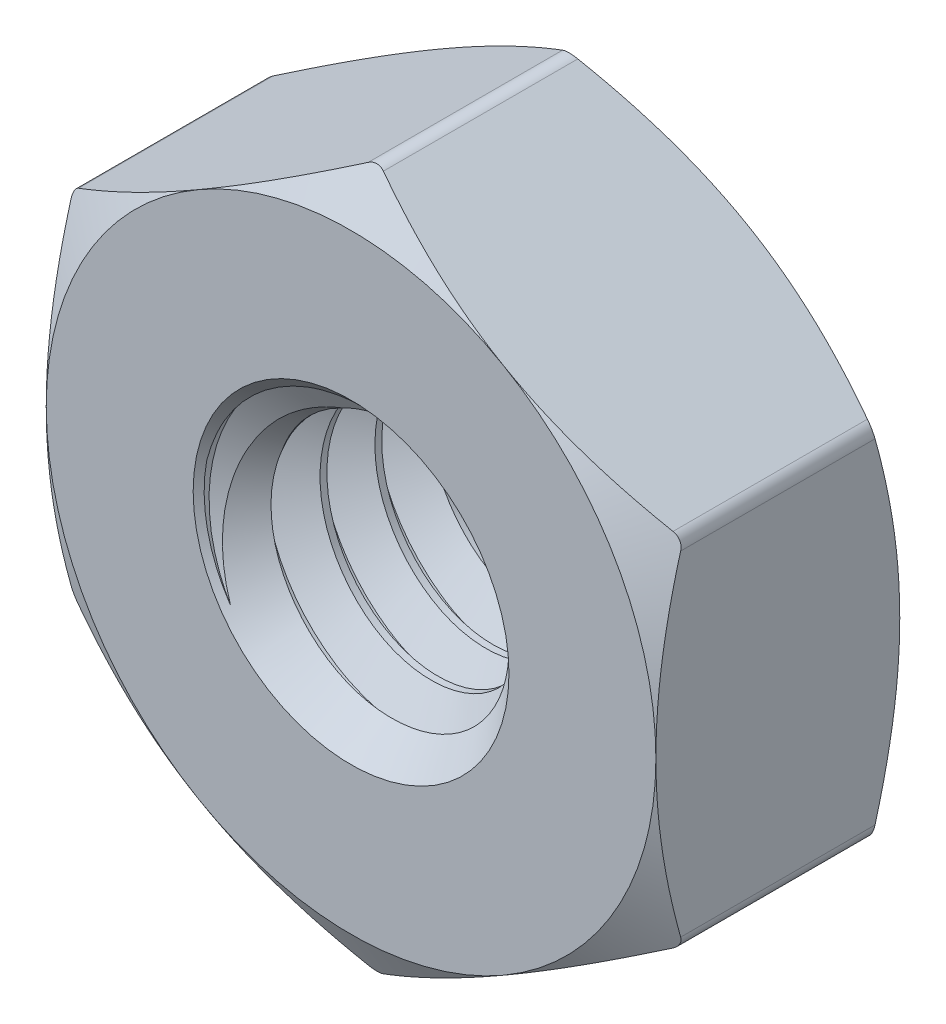
SolidWorks part; units mm, degrees
ref_plane "Front" through (0, 0, 0) normal (0, 0, 1) x (1, 0, 0)
ref_plane "Top" through (0, 0, 0) normal (0, 1, 0) x (1, 0, 0)
ref_plane "Right" through (0, 0, 0) normal (1, 0, 0) x (0, 0, -1)
sketch "Sketch1" plane through (0, 0, 0) normal (0, 0, 1) x (1, 0, 0)
  line L0 (0, 1.25) -> (0, 0.8) construction
  line L1 (-2.5, 1.4434) -> (-2.5, -1.4434)
  line L2 (-2.5, -1.4434) -> (0, -2.8868)
  line L3 (0, -2.8868) -> (2.5, -1.4434)
  line L4 (2.5, -1.4434) -> (2.5, 1.4434)
  line L5 (2.5, 1.4434) -> (0, 2.8868)
  line L6 (0, 2.8868) -> (-2.5, 1.4434)
  circle A0 centre (0, 0) radius 2.5 construction
  circle A1 centre (0, 0) radius 1.25 construction
  point P10 (0, 1.25)
  dimension "Width" = 5
  dimension "Thread Size" = 2.5
  dimension "Thread Pitch" = 0.45
sketch "Sketch2" plane through (0, 0, 0) normal (1, 0, 0) x (0, 0, -1)
  line L0 (-1, 0) -> (1, 0) construction
  line L1 (-1, 2.8868) -> (1, 2.8868) construction
  dimension "Height" = 2
sketch "Sketch15" plane through (0, 0, 0) normal (0, 0, 1) x (1, 0, 0)
  line L1 (0, 2.8868) -> (-2.5, 1.4434)
  line L2 (-2.5, 1.4434) -> (-2.5, -1.4434)
  line L3 (-2.5, -1.4434) -> (0, -2.8868)
  line L4 (0, -2.8868) -> (2.5, -1.4434)
  line L5 (2.5, -1.4434) -> (2.5, 1.4434)
  line L6 (2.5, 1.4434) -> (0, 2.8868)
  circle A0 centre (0, 0) radius 2.5 construction
extrude "Boss-Extrude2" add sketch "Sketch15" along normal mid plane 2
sketch "Sketch16" plane through (0, 0, 0) normal (0, 0, 1) x (1, 0, 0)
  circle A0 centre (0, 0) radius 1.25 construction
  circle A1 centre (0, 0) radius 1.25
sketch "Sketch4" plane through (0, 0, -1) normal (0, 0, -1) x (-1, 0, 0)
  circle A0 centre (0, 0) radius 1.25 construction
  circle A1 centre (0, 0) radius 1.25
extrude "Cut-Extrude4" cut sketch "Sketch16" against normal through all both and the other way through all
sketch "Sketch7" plane through (0, 0, 1) normal (0, 0, 1) x (1, 0, 0)
  circle A0 centre (0, 0) radius 2.5 construction
  circle A1 centre (0, 0) radius 2.5
extrude "Cut-Extrude5" cut sketch "Sketch7" against normal through all draft 60 flip side to cut
mirror "Mirror4" about plane through (0, 0, 0) normal (0, 0, 1) of "Cut-Extrude5"
fillet "Fillet2" radius 0.125 6 edges at (-2.5, 1.4434, 0) (-2.5, -1.4434, 0) (0, -2.8868, 0) (2.5, -1.4434, 0) (2.5, 1.4434, 0) (0, 2.8868, 0)
sketch "Sketch8" plane through (0, 0, 1) normal (0, 0, 1) x (1, 0, 0)
  line L0 (0.3235, -1.2074) -> (0, 0) construction
  line L2 (0, 1.25) -> (0, 0.8) construction
  circle A0 centre (0, 0) radius 1.25 construction
  point P0 (0.3235, -1.2074)
  dimension "D1" = 15
sketch "Sketch13" plane through (0, 0, -1) normal (0, 0, -1) x (-1, 0, 0)
  circle A0 centre (0, 0) radius 1.25 construction
  circle A1 centre (0, 0) radius 1.25
extrude "Boss-Extrude1" add sketch "Sketch13" against normal up to surface (2 mm away) separate body up to face at (1.25, 0, 1)
curve "Helix/Spiral3" pitch 0.45 height 2.9 radius 1.25 centre (0, 0, -1) axis (0, 0, 1) start towards (0, 1, 0)
sketch "Sketch12" plane through (0, 0, 0) normal (1, 0, 0) x (0, 0, -1)
  line L0 (1.3938, 1.25) -> (1, 1.25)
  line L1 (1.3938, 1.25) -> (1.225, 0.9577)
  line L2 (1.225, 0.9577) -> (1.1688, 0.9577)
  line L3 (1.1688, 0.9577) -> (1, 1.25)
  line L4 (1.1969, 0.9577) -> (1.1969, 1.25) construction
  line L5 (1.0844, 1.1039) -> (1.3094, 1.1039) construction
  dimension "D1" = 60
  dimension "D2" = 0.0563
  dimension "D3" = 0.225
sweep "Cut-Sweep1" cut profiles "Sketch12" path "Helix/Spiral3" align with end faces yes
sketch "Sketch17" plane through (0, 0, 1) normal (0, 0, 1) x (1, 0, 0)
  circle A1 centre (0, 0) radius 1.25
  circle A2 centre (0, 0) radius 1.25
  dimension "D1" = 0
extrude "Boss-Extrude3" add sketch "Sketch17" against normal up to surface (2 mm away) up to face at (1.25, 0, -1)
combine bodies "Combine1" operation type subtract main body 127 bodies to subtract 118
sketch "Sketch10" plane through (0, 0, 1) normal (0, 0, 1) x (1, 0, 0)
  circle A0 centre (0, 0) radius 1.25 construction
  circle A1 centre (0, 0) radius 1.25 construction
  circle A2 centre (0, 0) radius 1.295
  dimension "D1" = 0.045
extrude "Cut-Extrude2" cut sketch "Sketch10" against normal through all draft 45
sketch "Sketch11" plane through (0, 0, -1) normal (0, 0, -1) x (-1, 0, 0)
  circle A1 centre (0, 0) radius 1.295 construction
  circle A2 centre (0, 0) radius 1.295
extrude "Cut-Extrude3" cut sketch "Sketch11" against normal through all draft 45
equation "\"D1\"= \"Height@Sketch2\""
equation "\"D3@Helix/Spiral3\"=\"Height@Sketch2\"+\"Thread Pitch@Sketch1\"*2"
equation "\"D4@Helix/Spiral3\"=\"Thread Pitch@Sketch1\""
equation "\"D2@Sketch12\" = \"D4@Helix/Spiral3\"*.125"
equation "\"D3@Sketch12\" = \"D4@Helix/Spiral3\"*.50"
equation "\"D1@Boss-Extrude2\"=\"Height@Sketch2\""
equation "\"D1@Fillet2\"=\"Width@Sketch1\"*0.025"
equation "\"D1@Sketch10\"=\"Thread Pitch@Sketch1\"*0.1"
